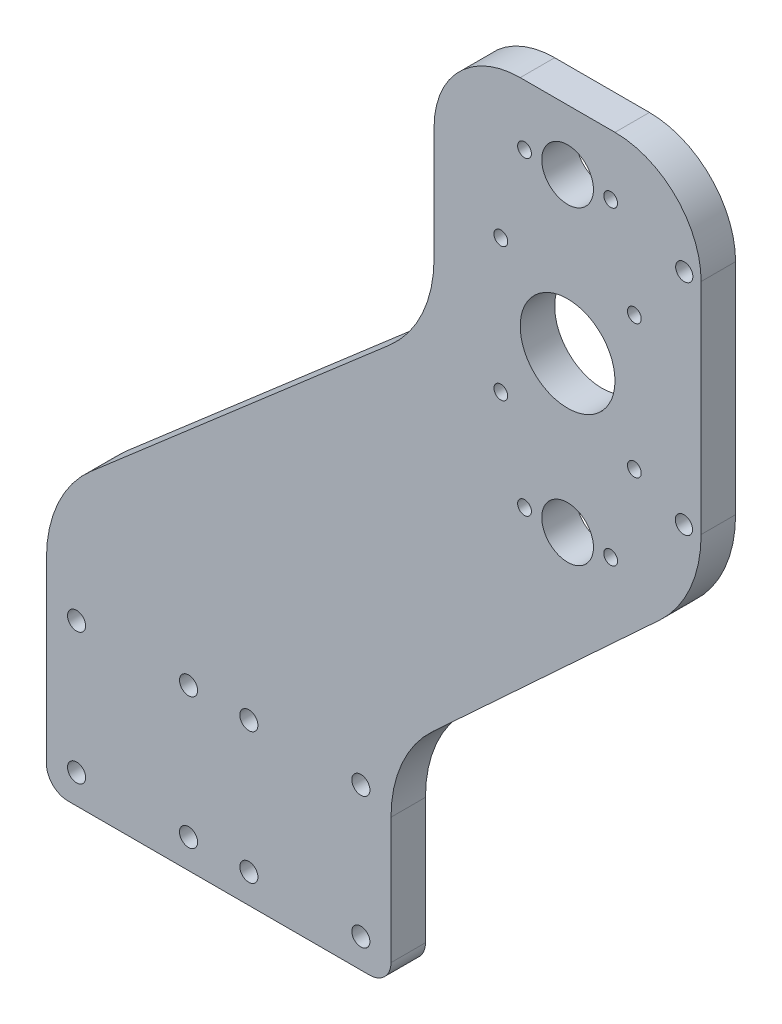
SolidWorks part; units mm, degrees
ref_plane "Front Plane" through (0, 0, 0) normal (0, 0, 1) x (1, 0, 0)
ref_plane "Top Plane" through (0, 0, 0) normal (0, 1, 0) x (1, 0, 0)
ref_plane "Right Plane" through (0, 0, 0) normal (1, 0, 0) x (0, 0, -1)
sketch "Sketch1" plane through (0, 0, 0) normal (0, 0, 1) x (1, 0, 0)
  line L0 (-23.731, -89.4451) -> (-23.731, -15.4242) construction
  line L1 (-58.731, -89.4451) -> (11.269, -89.4451)
  line L2 (-63.731, -84.4451) -> (-63.731, -43.1503)
  line L3 (-63.731, -84.4451) -> (-23.731, -84.4451) construction
  line L4 (16.269, -84.4451) -> (16.269, -55.2061)
  line L5 (46.269, 108.4996) -> (68.269, 108.4996)
  line L6 (26.269, 88.4996) -> (26.269, 62.2048)
  line L7 (57.269, 108.4996) -> (57.269, 22.5596) construction
  line L8 (88.269, 88.4996) -> (88.269, 37.6266)
  line L9 (-43.731, -67.4451) -> (-43.731, -84.4451) construction
  line L10 (-56.731, -52.1951) -> (-30.731, -52.1951) construction
  line L11 (15.9089, 39.5272) -> (-53.371, -20.4728)
  line L12 (78.6402, 15.6036) -> (25.8977, -33.1831)
  line L13 (-56.731, -52.1951) -> (-56.731, -82.6951) construction
  line L14 (-56.731, -82.6951) -> (-30.731, -82.6951) construction
  line L15 (-30.731, -52.1951) -> (-30.731, -82.6951) construction
  line L16 (-56.731, -52.1951) -> (-30.731, -82.6951) construction
  line L17 (-56.731, -82.6951) -> (-30.731, -52.1951) construction
  line L18 (57.269, 94.4996) -> (57.269, 22.5596) construction
  line L20 (41.769, 43.0296) -> (72.769, 43.0296) construction
  line L21 (41.769, 43.0296) -> (41.769, 74.0296) construction
  line L22 (41.769, 74.0296) -> (72.769, 74.0296) construction
  line L23 (72.769, 43.0296) -> (72.769, 74.0296) construction
  line L24 (41.769, 43.0296) -> (72.769, 74.0296) construction
  line L25 (41.769, 74.0296) -> (72.769, 43.0296) construction
  arc A0 (78.6402, 15.6036) -> (88.269, 37.6266) centre (58.269, 37.6266) ccw
  arc A1 (15.9089, 39.5272) -> (26.269, 62.2048) centre (-3.731, 62.2048) ccw
  arc A2 (16.269, -55.2061) -> (25.8977, -33.1831) centre (46.269, -55.2061) cw
  arc A3 (-63.731, -43.1503) -> (-53.371, -20.4728) centre (-33.731, -43.1503) cw
  arc A4 (88.269, 88.4996) -> (68.269, 108.4996) centre (68.269, 88.4996) ccw
  arc A5 (46.269, 108.4996) -> (26.269, 88.4996) centre (46.269, 88.4996) ccw
  arc A6 (16.269, -84.4451) -> (11.269, -89.4451) centre (11.269, -84.4451) cw
  arc A7 (-58.731, -89.4451) -> (-63.731, -84.4451) centre (-58.731, -84.4451) cw
  circle A8 centre (-56.731, -52.1951) radius 2.1
  circle A9 centre (-30.731, -52.1951) radius 2.1
  circle A10 centre (-30.731, -82.6951) radius 2.1
  circle A11 centre (-56.731, -82.6951) radius 2.1
  circle A12 centre (9.269, -82.6951) radius 2.1
  circle A13 centre (-16.731, -82.6951) radius 2.1
  circle A14 centre (-16.731, -52.1951) radius 2.1
  circle A15 centre (9.269, -52.1951) radius 2.1
  circle A16 centre (57.269, 94.4996) radius 6
  circle A17 centre (57.269, 22.5596) radius 6
  circle A18 centre (57.269, 58.5296) radius 11
  circle A19 centre (41.769, 74.0296) radius 1.6
  circle A20 centre (72.769, 74.0296) radius 1.6
  circle A21 centre (72.769, 43.0296) radius 1.6
  circle A22 centre (41.769, 43.0296) radius 1.6
  circle A23 centre (84.269, 37.6266) radius 2
  circle A24 centre (84.3518, 88.5185) radius 2
  circle A25 centre (47.269, 94.4996) radius 1.6
  circle A26 centre (47.269, 22.5596) radius 1.6
  circle A27 centre (67.269, 94.4996) radius 1.6
  circle A28 centre (67.269, 22.5596) radius 1.6
  point P0 (0, 0)
  point P1 (57.269, 82.2289)
  point P15 (26.269, 48.4996)
  point P20 (-63.731, -29.4451)
  point P23 (88.269, 108.4996)
  point P26 (26.269, 108.4996)
  point P29 (16.269, -89.4451)
  point P32 (-63.731, -89.4451)
  point P35 (-43.731, -67.4451)
  dimension "D5" = 30
  dimension "D6" = 20
  dimension "D7" = 5
  dimension "D14" = 71.94
  dimension "D12" = 31
  dimension "D17" = 4
  dimension "D18" = 10
  dimension "D19" = 10
  dimension "D1" = 80
  dimension "D2" = 22
  dimension "D3" = 90
  dimension "D4" = 60
  dimension "D8" = 26
  dimension "D9" = 60
  dimension "D10" = 22
  dimension "D11" = 60
  dimension "D13" = 30.5
  dimension "D15" = 14
  dimension "D16" = 31
extrude "Boss-Extrude1" add sketch "Sketch1" along normal blind 8
